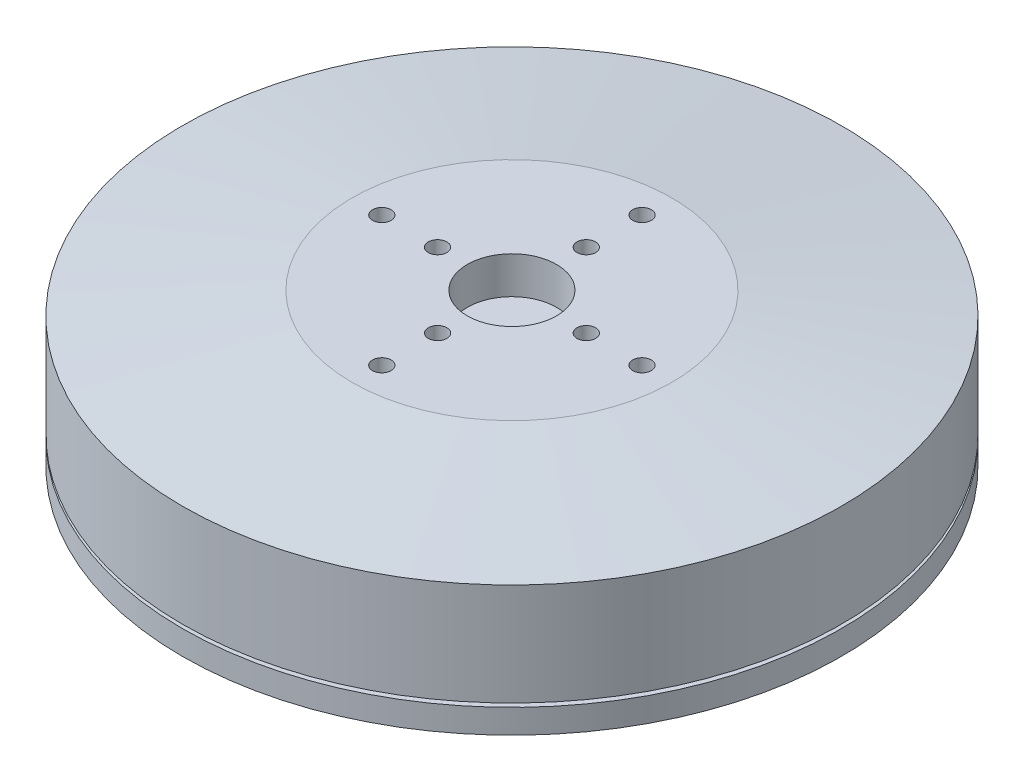
SolidWorks part; units mm, degrees
ref_plane "Спереди" through (0, 0, 0) normal (0, 0, 1) x (1, 0, 0)
ref_plane "Сверху" through (0, 0, 0) normal (0, 1, 0) x (1, 0, 0)
ref_plane "Справа" through (0, 0, 0) normal (1, 0, 0) x (0, 0, -1)
ref_axis "Axis1" through (0, -1.1797, 0) along (0, 1, 0)
sketch "Sketch1" plane through (0, 0, 0) normal (0, 0, 1) x (1, 0, 0)
  line L0 (0, 0) -> (0, -6208.3027) construction
  line L1 (0, -10.75) -> (0, 10.75)
  line L2 (0, 10.75) -> (-21.5, 10.75)
  line L3 (-21.5, 10.75) -> (-44.325, 7.75)
  line L4 (-44.325, 7.75) -> (-44.325, -6)
  line L5 (-44.325, -6) -> (-40.7625, -6)
  line L6 (-40.7625, -6) -> (-40.7625, -6.5)
  line L7 (-40.7625, -6.5) -> (-44.325, -6.5)
  line L8 (-44.325, -6.5) -> (-44.325, -9.75)
  line L9 (-44.325, -9.75) -> (-35, -10.75)
  line L10 (-35, -10.75) -> (0, -10.75)
  point P18 (-40.7625, -6.25)
  dimension "D1" = 0.5
  dimension "D2" = 88.65
  dimension "D3" = 43
  dimension "D4" = 70
  dimension "D5" = 21.5
  dimension "D6" = 3
  dimension "D7" = 1
  dimension "D8" = 4.5
revolve "Revolve1" add sketch "Sketch1" angle 360 about L0
hole_wizard "M3x0.5 Tapped Hole1" positions "Sketch2" profile "Sketch3" tap size "M3x0.5" standard "ANSI Metric"
sketch "Sketch2" plane through (0, 10.75, 0) normal (0, 1, 0) x (1, 0, 0)
  point P0 (0, 17.5)
  point P2 (0, 10)
  point P10 (17.5, 0)
  point P11 (10, 0)
  point P12 (0, -17.5)
  point P13 (0, -10)
  point P14 (-17.5, 0)
  point P15 (-10, 0)
  dimension "D1" = 17.5
  dimension "D2" = 10
  dimension "D3" = 4
sketch "Sketch3" plane through (0, 10.75, -17.5) normal (1, 0, 0) x (0, 0, 1)
  line L0 (0, 0) -> (0, 7.2511)
  line L1 (0, 7.2511) -> (1.25, 6.5)
  line L2 (1.25, 6.5) -> (1.25, 0)
  line L5 (1.25, 0) -> (0, 0)
  line L10 (0, 7.2511) -> (-1.25, 6.5) construction
  line L11 (0, -6.35) -> (0, 107.95) construction
  dimension "Tap Drill Dia." = 2.5
  dimension "Tap Drill Depth" = 6.5
  dimension "Drill Angle" = 118
cosmetic thread "Hole Thread2" parameters "D1"=4, "D2"=3
cosmetic thread "Hole Thread3" parameters "D1"=4, "D2"=3
cosmetic thread "Hole Thread4" parameters "D1"=4, "D2"=3
cosmetic thread "Hole Thread5" parameters "D1"=4, "D2"=3
cosmetic thread "Hole Thread6" parameters "D1"=4, "D2"=3
cosmetic thread "Hole Thread7" parameters "D1"=4, "D2"=3
cosmetic thread "Hole Thread8" parameters "D1"=4, "D2"=3
cosmetic thread "Hole Thread9" parameters "D1"=4, "D2"=3
sketch "Sketch4" plane through (0, 10.75, 0) normal (0, 1, 0) x (1, 0, 0)
  circle A0 centre (0, 0) radius 6
  dimension "D1" = 12
extrude "Cut-Extrude1" cut sketch "Sketch4" against normal blind 5
hole_wizard "M3x0.5 Tapped Hole2" positions "Sketch5" profile "Sketch6" tap size "M3x0.5" standard "ANSI Metric"
sketch "Sketch5" plane through (0, -10.75, 0) normal (0, -1, 0) x (-1, 0, 0)
  point P0 (0, 15)
  point P9 (15, 0)
  point P10 (0, -15)
  point P11 (-15, 0)
  dimension "D1" = 15
  dimension "D2" = 4
sketch "Sketch6" plane through (0, -10.75, -15) normal (1, 0, 0) x (0, 0, -1)
  line L0 (0, 0) -> (0, 7.2511)
  line L1 (0, 7.2511) -> (1.25, 6.5)
  line L2 (1.25, 6.5) -> (1.25, 0)
  line L5 (1.25, 0) -> (0, 0)
  line L10 (0, 7.2511) -> (-1.25, 6.5) construction
  line L11 (0, -6.35) -> (0, 107.95) construction
  dimension "Tap Drill Dia." = 2.5
  dimension "Tap Drill Depth" = 6.5
  dimension "Drill Angle" = 118
cosmetic thread "Hole Thread11" parameters "D1"=4, "D2"=3
cosmetic thread "Hole Thread12" parameters "D1"=4, "D2"=3
cosmetic thread "Hole Thread13" parameters "D1"=4, "D2"=3
cosmetic thread "Hole Thread14" parameters "D1"=4, "D2"=3
sketch "Sketch8" plane through (0, 0, 0) normal (0, 1, 0) x (1, 0, 0)
  line L0 (0, 0) -> (0, -50000) construction
  line L1 (0, 0) -> (-35355.3391, -35355.3391) construction
  point P5 (-23.0464, -23.0464)
  dimension "D1" = 45
ref_plane "45 deg plane" through (0, 0, 0) normal (0.7071, 0, 0.7071) x (0.7071, 0, -0.7071)
